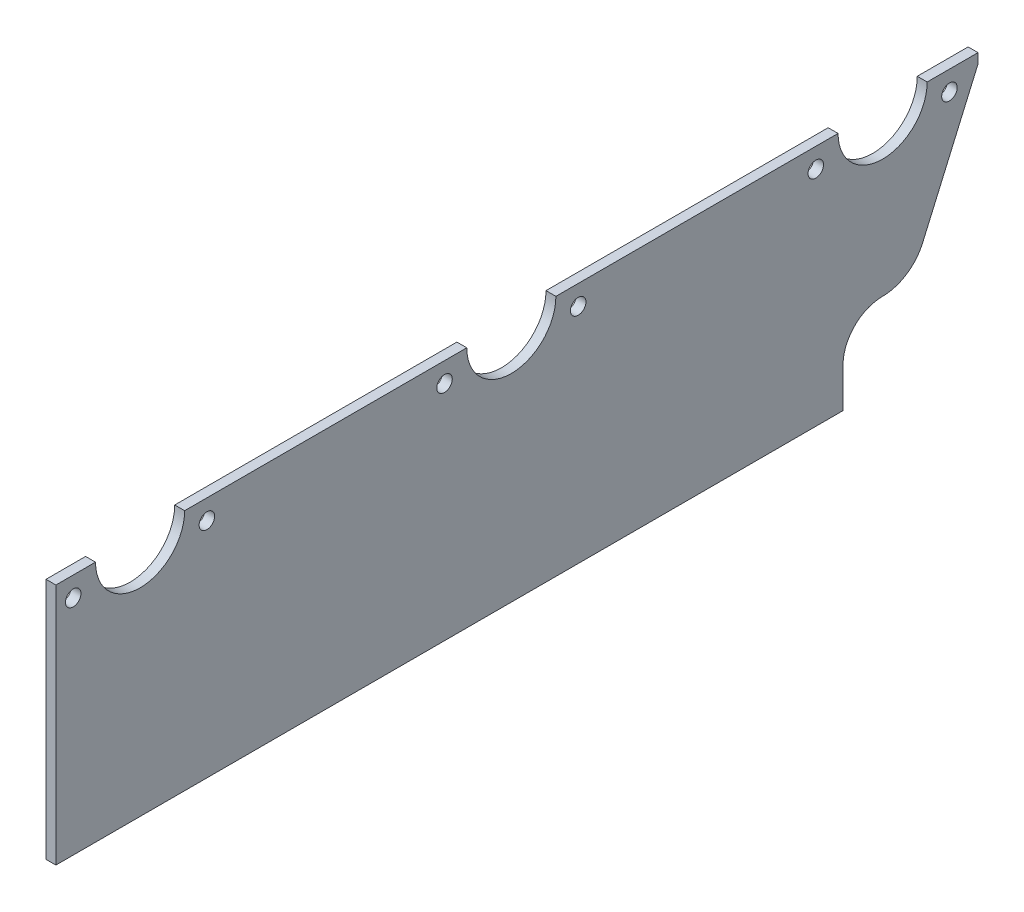
SolidWorks part; units mm, degrees
material "6061 Alloy"
ref_plane "Front Plane" through (0, 0, 0) normal (0, 0, 1) x (1, 0, 0)
ref_plane "Top Plane" through (0, 0, 0) normal (0, 1, 0) x (1, 0, 0)
ref_plane "Right Plane" through (0, 0, 0) normal (1, 0, 0) x (0, 0, -1)
sketch "Sketch1" plane through (0, 0, 0) normal (1, 0, 0) x (0, 0, -1)
  line L0 (-12.7, -12.7) -> (-265.1125, -12.7)
  line L1 (-265.1125, -12.7) -> (-265.1125, 65.0875)
  line L2 (-265.1125, 65.0875) -> (-252.4125, 65.0875)
  line L3 (-223.8375, 65.0875) -> (-133.35, 65.0875)
  line L4 (-104.775, 65.0875) -> (-14.2875, 65.0875)
  line L5 (14.2875, 65.0875) -> (30.5881, 65.0875)
  line L7 (-265.1125, 12.7) -> (12.8078, 12.7) construction
  line L8 (-12.7, -12.7) -> (-12.7, 0)
  line L9 (0, 12.4079) -> (0, 12.7) construction
  line L10 (12.8078, 21.0914) -> (30.5881, 61.9125)
  line L11 (30.5881, 65.0875) -> (30.5881, 61.9125)
  arc A3 (0, 12.7) -> (12.8078, 21.0914) centre (0, 26.67) ccw
  arc A4 (0, 12.7) -> (-12.7, 0) centre (0, 0) ccw
  circle A5 centre (0, 0) radius 12.4079 construction
  arc A6 (-252.4125, 65.0875) -> (-223.8375, 65.0875) centre (-238.125, 65.0875) ccw
  arc A7 (-133.35, 65.0875) -> (-104.775, 65.0875) centre (-119.0625, 65.0875) ccw
  arc A8 (-14.2875, 65.0875) -> (14.2875, 65.0875) centre (0, 65.0875) ccw
  point P4 (-138.9062, -12.7)
  point P16 (-1.5704, 64.9983)
  point P21 (0, 0)
  dimension "D1" = 25.4
  dimension "D3" = 30.5881
  dimension "D5" = 28.575
  dimension "D6" = 38.1
  dimension "D7" = 13.97
  dimension "D8" = 12.7
  dimension "D10" = 24.8158
  dimension "D13" = 3.175
  dimension "D2" = 0
  dimension "D4" = 12.7
  dimension "D9" = 12.7
  dimension "D11" = 238.125
  dimension "D12" = 238.125
extrude "Boss-Extrude1" add sketch "Sketch1" along normal blind 3.175
hole_wizard "#10 Clearance Hole1" positions "Sketch2" profile "Sketch3" hole size "#10" standard "ANSI Inch" end condition through all
sketch "Sketch2" plane through (3.175, 0, 0) normal (1, 0, 0) x (0, 0, -1)
  line L0 (-259.5563, 58.7375) -> (-216.6938, 58.7375) construction
  line L2 (-140.4938, 58.7375) -> (-97.6313, 58.7375) construction
  line L4 (-21.4313, 58.7375) -> (21.4312, 58.7375) construction
  line L6 (-252.4125, 65.0875) -> (-265.1125, 65.0875) construction
  line L7 (-238.125, 58.7375) -> (-238.125, 65.0875) construction
  line L9 (-119.0625, 65.0875) -> (-119.0625, 58.7375) construction
  line L11 (0, 65.0875) -> (0, 58.7375) construction
  point P0 (-259.5563, 58.7375)
  point P2 (-216.6938, 58.7375)
  point P4 (-140.4938, 58.7375)
  point P6 (-97.6313, 58.7375)
  point P8 (-21.4313, 58.7375)
  point P10 (21.4312, 58.7375)
  dimension "D1" = 42.8625
  dimension "D2" = 6.35
sketch "Sketch3" plane through (3.175, 58.7375, 259.5563) normal (0, 1, 0) x (0, 0, -1)
  line L0 (0, 0) -> (0, 3.175)
  line L1 (0, 3.175) -> (2.4892, 3.175)
  line L2 (2.4892, 3.175) -> (2.4892, 0)
  line L5 (2.4892, 0) -> (0, 0)
  line L11 (0, -6.35) -> (0, 107.95) construction
  dimension "Thru Hole Dia." = 4.9784
  dimension "Thru Hole Depth" = 3.175
